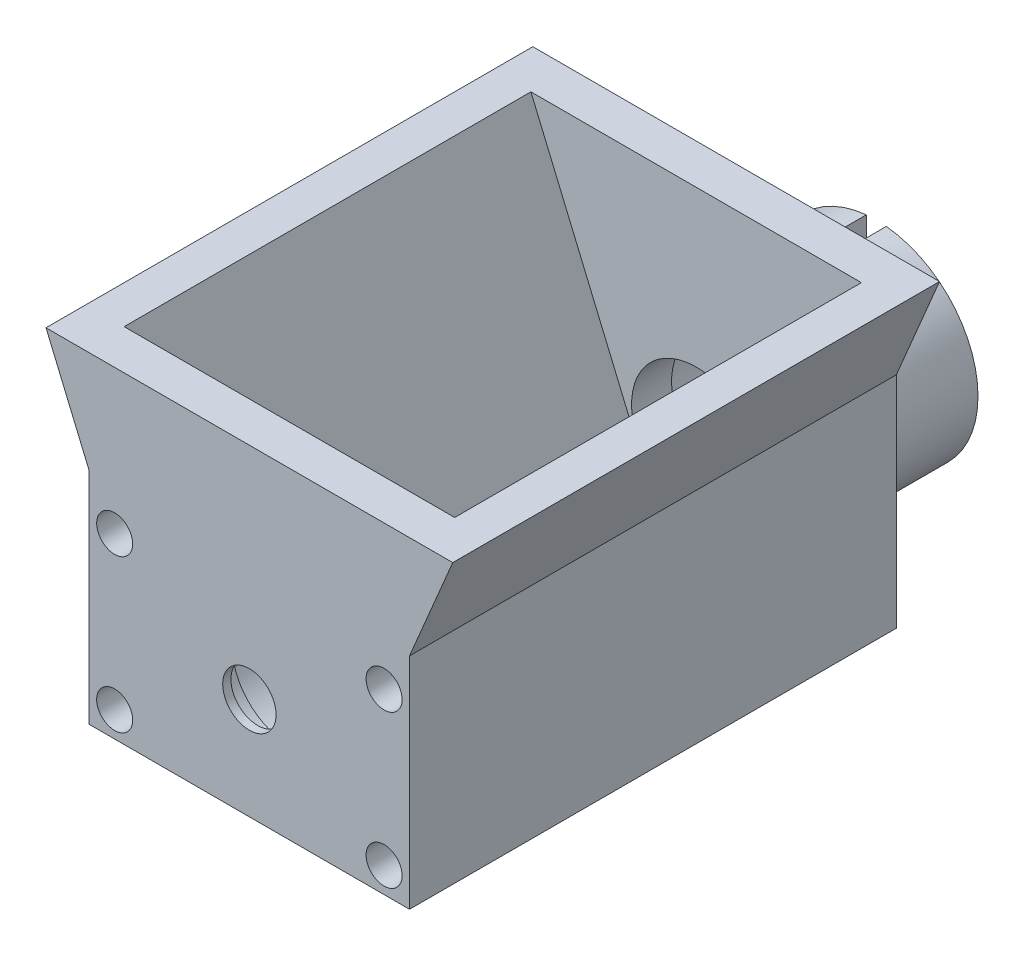
SolidWorks part; units mm, degrees
ref_plane "Front" through (0, 0, 0) normal (0, 0, 1) x (1, 0, 0)
ref_plane "Top" through (0, 0, 0) normal (0, 1, 0) x (1, 0, 0)
ref_plane "Right" through (0, 0, 0) normal (1, 0, 0) x (0, 0, -1)
sketch "Sketch1" plane through (0, 0, 0) normal (0, 0, 1) x (1, 0, 0)
  line L0 (0, 0) -> (0, 55) construction
  line L1 (23.3989, -9.8819) -> (50.8, 55)
  line L2 (50.8, 55) -> (-50.8, 55)
  line L3 (-23.3989, -9.8819) -> (-50.8, 55)
  circle A0 centre (0, 0) radius 16.129
  arc A1 (-23.3989, -9.8819) -> (23.3989, -9.8819) centre (0, 0) ccw
  dimension "D1" = 32.258
  dimension "D2" = 50.8
  dimension "D3" = 55
  dimension "D4" = 50.8
extrude "Boss-Extrude1" add sketch "Sketch1" along normal blind 10
sketch "Sketch2" plane through (0, 0, 10) normal (0, 0, 1) x (1, 0, 0)
  line L0 (-41.2789, 55) -> (-50.8, 55)
  line L3 (15.3189, -6.4695) -> (41.2789, 55)
  line L4 (50.8, 55) -> (-50.8, 55) construction
  line L5 (-15.3189, -6.4695) -> (-41.2789, 55)
  line L9 (-50.8, 55) -> (-23.3989, -9.8819)
  line L10 (23.3989, -9.8819) -> (50.8, 55)
  line L11 (50.8, 55) -> (-50.8, 55)
  line L12 (-50.8, 55) -> (-23.3989, -9.8819)
  line L13 (23.3989, -9.8819) -> (50.8, 55)
  line L14 (50.8, 55) -> (41.2789, 55)
  circle A4 centre (0, 0) radius 16.629
  arc A5 (-15.3189, -6.4695) -> (15.3189, -6.4695) centre (0, 0) ccw
  arc A6 (-23.3989, -9.8819) -> (23.3989, -9.8819) centre (0, 0) ccw
  arc A7 (-23.3989, -9.8819) -> (23.3989, -9.8819) centre (0, 0) ccw
  dimension "D1" = 0.5
  dimension "D2" = 0
extrude "Boss-Extrude2" add sketch "Sketch2" along normal blind 101.6
sketch "Sketch3" plane through (0, 0, 111.6) normal (0, 0, 1) x (1, 0, 0)
  line L0 (41.2789, 55) -> (-41.2789, 55)
  line L6 (-15.3189, -6.4695) -> (-41.2789, 55)
  line L7 (-41.2789, 55) -> (-50.8, 55)
  line L8 (-50.8, 55) -> (-23.3989, -9.8819)
  line L9 (23.3989, -9.8819) -> (50.8, 55)
  line L10 (50.8, 55) -> (41.2789, 55)
  line L11 (41.2789, 55) -> (15.3189, -6.4695)
  line L13 (-41.2789, 55) -> (-50.8, 55)
  line L14 (-50.8, 55) -> (-23.3989, -9.8819)
  line L15 (23.3989, -9.8819) -> (50.8, 55)
  line L16 (50.8, 55) -> (41.2789, 55)
  arc A2 (-15.3189, -6.4695) -> (15.3189, -6.4695) centre (0, 0) ccw
  arc A3 (-23.3989, -9.8819) -> (23.3989, -9.8819) centre (0, 0) ccw
  arc A5 (-23.3989, -9.8819) -> (23.3989, -9.8819) centre (0, 0) ccw
  dimension "D1" = 0
extrude "Boss-Extrude3" add sketch "Sketch3" along normal blind 10
sketch "Sketch4" plane through (0, 0, 0) normal (0, 0, -1) x (-1, 0, 0)
  circle A0 centre (0, 0) radius 19.05
  circle A1 centre (0, 0) radius 25.4
  dimension "D1" = 38.1
extrude "Boss-Extrude4" add sketch "Sketch4" along normal blind 35
sketch "Sketch5" plane through (0, 0, -35) normal (0, 0, -1) x (-1, 0, 0)
  line L0 (0, 25.4) -> (0, -25.4) construction
  line L1 (-2.5, 25.4) -> (-2.5, -25.4)
  line L2 (2.5, 25.4) -> (2.5, -25.4)
  line L3 (2.5, 25.4) -> (-2.5, 25.4)
  line L4 (2.5, -25.4) -> (-2.5, -25.4)
  circle A0 centre (0, 0) radius 25.4 construction
  dimension "D1" = 2.5
  dimension "D2" = 2.5
extrude "Cut-Extrude1" cut sketch "Sketch5" against normal blind 20
sketch "Sketch6" plane through (0, 0, 111.6) normal (0, 0, -1) x (-1, 0, 0)
  circle A0 centre (0, 0) radius 16.129 construction
  circle A1 centre (0, 0) radius 16.129 construction
  circle A2 centre (0, -0.6177) radius 14.3129
  dimension "D1" = 28.6258
extrude "Cut-Extrude2" cut sketch "Sketch6" against normal blind 7.9375
sketch "Sketch7" plane through (0, 0, 119.5375) normal (0, 0, -1) x (-1, 0, 0)
  circle A0 centre (0, 0) radius 6.6675
  dimension "D1" = 13.335
extrude "Cut-Extrude3" cut sketch "Sketch7" against normal up to next
sketch "Sketch8" plane through (0, 0, 121.6) normal (0, 0, 1) x (1, 0, 0)
  line L0 (-40, -25.4) -> (40, -25.4)
  line L1 (40, -25.4) -> (40, 24.6)
  line L3 (23.3989, -9.8819) -> (50.8, 55) construction
  line L4 (0, -25.4) -> (0, 55) construction
  line L5 (50.8, 55) -> (-50.8, 55) construction
  line L6 (-23.3989, -9.8819) -> (-37.9614, 24.6)
  line L8 (-40, -25.4) -> (-40, 24.6)
  line L9 (50.8, 55) -> (-50.8, 55)
  line L10 (-50.8, 55) -> (-23.3989, -9.8819)
  line L11 (23.3989, -9.8819) -> (50.8, 55)
  line L14 (23.3989, -9.8819) -> (37.9614, 24.6)
  line L15 (40, 24.6) -> (40, 29.4271)
  line L16 (40, 29.4271) -> (37.9614, 24.6)
  line L17 (-40, 24.6) -> (-40, 29.4271)
  line L18 (-50.8, 55) -> (-23.3989, -9.8819) construction
  line L19 (-40, 29.4271) -> (-37.9614, 24.6)
  circle A1 centre (0, 0) radius 6.6675 construction
  arc A3 (-23.3989, -9.8819) -> (23.3989, -9.8819) centre (0, 0) ccw
  arc A4 (-23.3989, -9.8819) -> (23.3989, -9.8819) centre (0, 0) ccw
  point P2 (0, -25.4)
  dimension "D1" = 40
  dimension "D4" = 0
  dimension "D2" = 0
extrude "Boss-Extrude5" add sketch "Sketch8" against normal up to surface (121.6 mm away) up to face at (16.129, 0, 0)
fillet "Fillet1" radius 10 1 edges at (-25.4, 0, 0)
sketch "Sketch9" plane through (0, 0, 121.6) normal (0, 0, 1) x (1, 0, 0)
  circle A0 centre (33.65, 19.05) radius 4.5
  circle A1 centre (-33.65, 19.05) radius 4.5
  circle A2 centre (-33.65, -19.05) radius 4.5
  circle A3 centre (33.65, -19.05) radius 4.5
  dimension "D1" = 9
extrude "Cut-Extrude4" cut sketch "Sketch9" against normal blind 10
